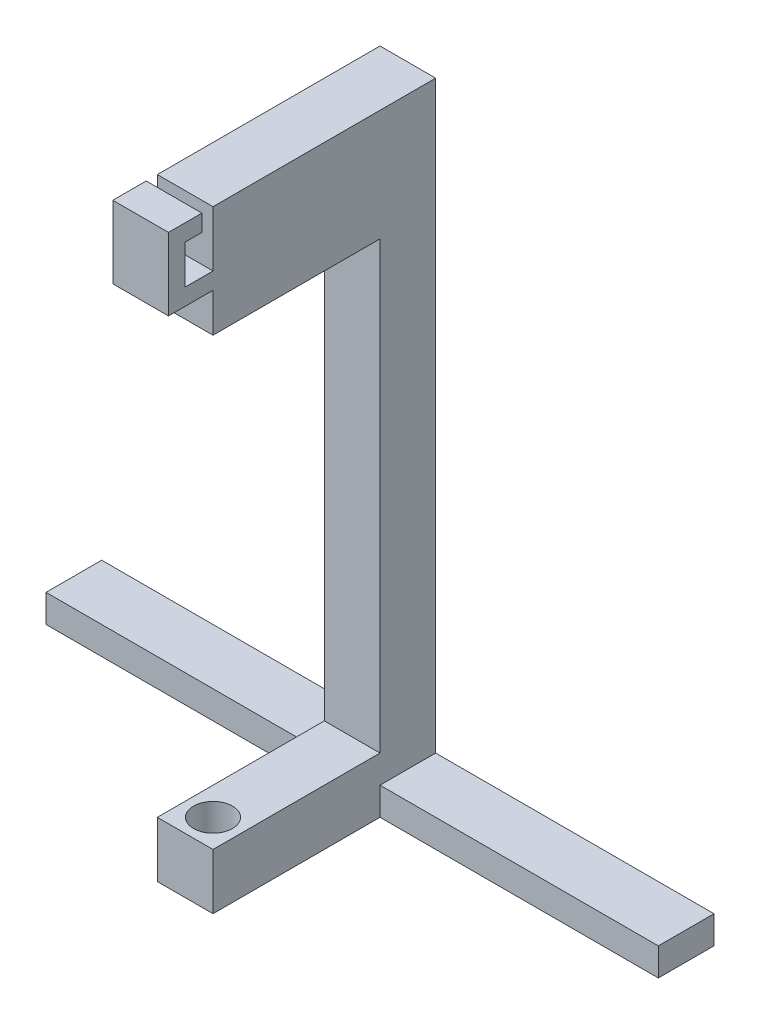
SolidWorks part; units mm, degrees
ref_plane "Přední rovina" through (0, 0, 0) normal (0, 0, 1) x (1, 0, 0)
ref_plane "Horní rovina" through (0, 0, 0) normal (0, 1, 0) x (1, 0, 0)
ref_plane "Pravá rovina" through (0, 0, 0) normal (1, 0, 0) x (0, 0, -1)
sketch "Skica1" plane through (0, 0, 0) normal (0, 0, 1) x (1, 0, 0)
  line L1 (0, 0) -> (10, 0)
  line L2 (0, 0) -> (0, 10)
  line L3 (0, 10) -> (10, 10)
  line L4 (10, 0) -> (10, 10)
  dimension "D1" = 10
  dimension "D2" = 10
extrude "Přidat vysunutím1" add sketch "Skica1" along normal blind 10
sketch "Skica2" plane through (0, 10, 0) normal (0, 1, 0) x (1, 0, 0)
  line L0 (10, -10) -> (10, 0) construction
  line L1 (10, 0) -> (0, 0) construction
  circle A0 centre (5, -5) radius 3.5
  dimension "D1" = 5
  dimension "D2" = 7
  dimension "D3" = 5
extrude "Odebrat vysunutím1" cut sketch "Skica2" against normal blind 5
sketch "Skica6" plane through (0, 0, 0) normal (0, 0, -1) x (-1, 0, 0)
  line L1 (-10, 10) -> (0, 10)
  line L2 (-10, 10) -> (-10, 0)
  line L3 (-10, 0) -> (0, 0)
  line L4 (0, 10) -> (0, 0)
extrude "Přidat vysunutím9" add sketch "Skica6" along normal blind 30
sketch "Skica7" plane through (0, 10, 0) normal (0, 1, 0) x (1, 0, 0)
  line L0 (10, -10) -> (10, 30) construction
  line L1 (0, 30) -> (10, 30)
  line L2 (0, 30) -> (0, 20)
  line L3 (0, 20) -> (10, 20)
  line L4 (10, 30) -> (10, 20)
  dimension "D1" = 10
extrude "Přidat vysunutím11" add sketch "Skica7" along normal blind 100
sketch "Skica8" plane through (0, 0, -20) normal (0, 0, 1) x (1, 0, 0)
  line L0 (10, 110) -> (10, 10) construction
  line L1 (0, 110) -> (10, 110)
  line L2 (0, 110) -> (0, 100)
  line L3 (0, 100) -> (10, 100)
  line L4 (10, 110) -> (10, 100)
  dimension "D1" = 10
extrude "Přidat vysunutím12" add sketch "Skica8" along normal blind 30
sketch "Skica9" plane through (0, 100, 0) normal (0, -1, 0) x (1, 0, 0)
  line L0 (10, 10) -> (10, -20) construction
  line L1 (0, 10) -> (10, 10)
  line L2 (0, 10) -> (0, 0)
  line L3 (0, 0) -> (10, 0)
  line L4 (10, 10) -> (10, 0)
extrude "Přidat vysunutím13" add sketch "Skica9" along normal blind 10
sketch "Skica10" plane through (0, 90, 0) normal (0, -1, 0) x (1, 0, 0)
  line L0 (10, 10) -> (0, 10) construction
  circle A0 centre (4.7979, 5) radius 3.5
  dimension "D1" = 7
  dimension "D2" = 5
extrude "Odebrat vysunutím2" cut sketch "Skica10" against normal blind 10
sketch "Skica11" plane through (10, 0, 0) normal (1, 0, 0) x (0, 0, -1)
  line L0 (-10, 0) -> (30, 0) construction
  line L1 (20, 0) -> (30, 0)
  line L2 (20, 0) -> (20, 5)
  line L3 (20, 5) -> (30, 5)
  line L4 (30, 0) -> (30, 5)
  line L5 (-10, 0) -> (-10, 10) construction
  dimension "D1" = 10
  dimension "D2" = 5
  dimension "D3" = 30
sketch "Skica20" plane through (0, 0, 0) normal (0, 0, -1) x (-1, 0, 0)
  line L1 (-10, 100) -> (0, 100)
  line L2 (-10, 100) -> (-10, 90)
  line L3 (-10, 90) -> (0, 90)
  line L4 (0, 100) -> (0, 90)
extrude "Přidat vysunutím21" add sketch "Skica20" along normal blind 20
extrude "Přidat vysunutím22" add sketch "Skica11" along normal blind 50 and the other way blind 60
extrude "Odebrat vysunutím7" cut sketch "Skica10<2>" against normal blind 15
sketch "Skica10<2>" plane through (0, 90, 0) normal (0, -1, 0) x (1, 0, 0) same geometry as "Skica10"
sketch "Skica21" plane through (0, 0, 10) normal (0, 0, 1) x (1, 0, 0)
  line L0 (0, 110) -> (0, 90) construction
  line L1 (0, 100) -> (10, 100)
  line L2 (0, 100) -> (0, 97)
  line L3 (0, 97) -> (10, 97)
  line L4 (10, 100) -> (10, 97)
  line L5 (10, 90) -> (10, 110) construction
  line L6 (10, 90) -> (0, 90) construction
  dimension "D1" = 3
  dimension "D2" = 7
extrude "Přidat vysunutím24" add sketch "Skica21" along normal blind 8
sketch "Skica22" plane through (0, 100, 0) normal (0, 1, 0) x (1, 0, 0)
  line L0 (10, -18) -> (10, -10) construction
  line L1 (0, -18) -> (10, -18)
  line L2 (0, -18) -> (0, -15)
  line L3 (0, -15) -> (10, -15)
  line L4 (10, -18) -> (10, -15)
  dimension "D1" = 3
extrude "Přidat vysunutím25" add sketch "Skica22" along normal blind 10
sketch "Skica23" plane through (0, 0, 15) normal (0, 0, -1) x (-1, 0, 0)
  line L0 (0, 110) -> (0, 100) construction
  line L1 (-10, 110) -> (0, 110)
  line L2 (-10, 110) -> (-10, 107)
  line L3 (-10, 107) -> (0, 107)
  line L4 (0, 110) -> (0, 107)
  dimension "D1" = 3
extrude "Přidat vysunutím26" add sketch "Skica23" along normal blind 3
